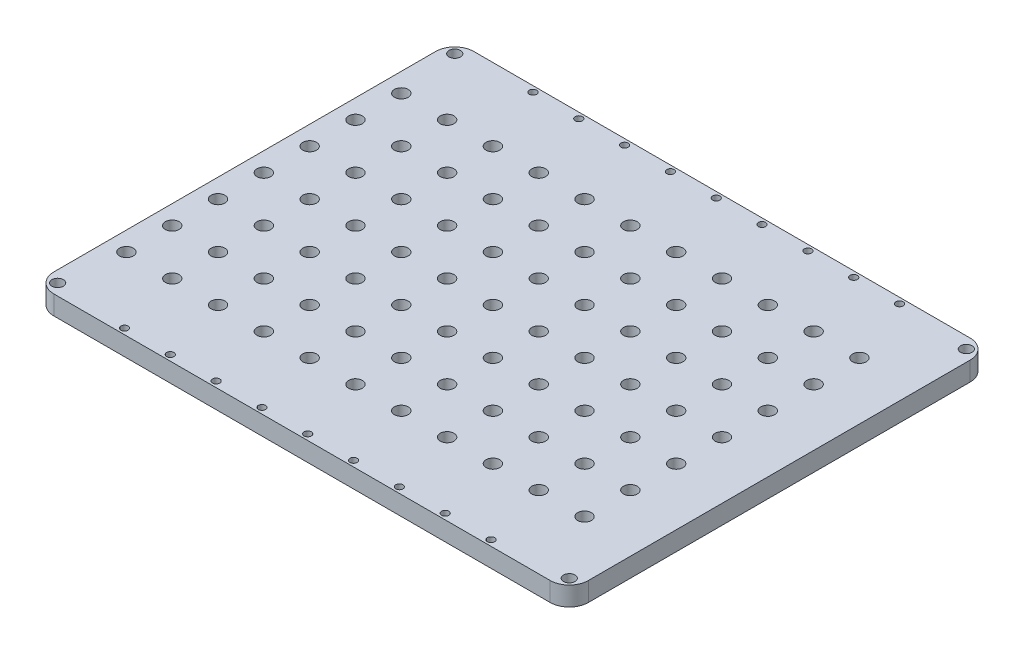
SolidWorks part; units mm, degrees
ref_plane "Front Plane" through (0, 0, 0) normal (0, 0, 1) x (1, 0, 0)
ref_plane "Top Plane" through (0, 0, 0) normal (0, 1, 0) x (1, 0, 0)
ref_plane "Right Plane" through (0, 0, 0) normal (1, 0, 0) x (0, 0, -1)
sketch "Sketch1" plane through (0, 0, 0) normal (0, 1, 0) x (1, 0, 0)
  line L1 (-70, 55) -> (70, 55)
  line L2 (-70, 55) -> (-70, -55)
  line L3 (-70, -55) -> (70, -55)
  line L4 (70, 55) -> (70, -55)
  line L5 (-70, 55) -> (70, -55) construction
  line L6 (-70, -55) -> (70, 55) construction
  point P0 (0, 0)
  dimension "D1" = 110
  dimension "D2" = 140
extrude "Boss-Extrude1" add sketch "Sketch1" along normal blind 5
fillet "Fillet1" radius 5 4 edges at (70, 2.5, -55) (70, 2.5, 55) (-70, 2.5, 55) (-70, 2.5, -55)
sketch "Sketch2" plane through (0, 5, 0) normal (0, 1, 0) x (1, 0, 0)
  line L4 (-68.5355, 53.5355) -> (-67.0011, 52.0011)
  line L8 (67, -50) -> (67, 50)
  line L9 (65, 52) -> (-65, 52)
  line L10 (-67, 50) -> (-67, -50)
  line L11 (-65, -52) -> (65, -52)
  line L12 (67, -50) -> (67, 50)
  line L13 (65, 52) -> (-65, 52)
  line L14 (-67, 50) -> (-67, -50)
  line L15 (-65, -52) -> (65, -52)
  arc A6 (-65, 55) -> (-70, 50) centre (-65, 50) ccw construction
  circle A7 centre (-67.0011, 52.0011) radius 1.5
  arc A8 (67, 50) -> (65, 52) centre (65, 50) ccw
  arc A9 (-65, 52) -> (-67, 50) centre (-65, 50) ccw
  arc A10 (-67, -50) -> (-65, -52) centre (-65, -50) ccw
  arc A11 (65, -52) -> (67, -50) centre (65, -50) ccw
  arc A12 (67, 50) -> (65, 52) centre (65, 50) ccw
  arc A13 (-65, 52) -> (-67, 50) centre (-65, 50) ccw
  arc A14 (-67, -50) -> (-65, -52) centre (-65, -50) ccw
  arc A15 (65, -52) -> (67, -50) centre (65, -50) ccw
  circle A16 centre (66.9989, 52.0011) radius 1.5
  circle A17 centre (66.9989, -51.9989) radius 1.5
  circle A18 centre (-67.0011, -51.9989) radius 1.5
  dimension "D2" = 2
  dimension "D1" = 3
  dimension "D3" = 2
extrude "Cut-Extrude1" cut sketch "Sketch2" against normal blind 5 contours A13 A7 | A7 A13 | A15 A17 | A15 A17 | A14 A18 | A14 A18 | A16 region at (67.1229, 5, 52.1229) region at (66.1833, 5, 51.1833) region at (-67.1248, 5, 52.1224) region at (-66.1845, 5, 51.1832) region at (-66.4442, 5, -51.4442) region at (-66.1844, 5, -51.1844)
sketch "Sketch3" plane through (0, 5, 0) normal (0, 1, 0) x (1, 0, 0)
  line L0 (0, -55) -> (0, -52)
  line L1 (-65, -55) -> (65, -55) construction
  circle A0 centre (0, -53.5) radius 0.95
  circle A1 centre (12, -53.5) radius 0.95
  circle A2 centre (24, -53.5) radius 0.95
  circle A3 centre (36, -53.5) radius 0.95
  circle A4 centre (48, -53.5) radius 0.95
  circle A5 centre (0, -53.5) radius 0.95
  circle A6 centre (12, -53.5) radius 0.95
  circle A7 centre (24, -53.5) radius 0.95
  circle A8 centre (36, -53.5) radius 0.95
  circle A9 centre (-12, -53.5) radius 0.95
  circle A10 centre (0, -53.5) radius 0.95
  circle A11 centre (12, -53.5) radius 0.95
  circle A12 centre (24, -53.5) radius 0.95
  circle A13 centre (-24, -53.5) radius 0.95
  circle A14 centre (-12, -53.5) radius 0.95
  circle A15 centre (0, -53.5) radius 0.95
  circle A16 centre (12, -53.5) radius 0.95
  circle A17 centre (-36, -53.5) radius 0.95
  circle A18 centre (-24, -53.5) radius 0.95
  circle A19 centre (-12, -53.5) radius 0.95
  circle A20 centre (0, -53.5) radius 0.95
  circle A21 centre (-12, -53.5) radius 0.95
  circle A22 centre (-24, -53.5) radius 0.95
  circle A23 centre (-36, -53.5) radius 0.95
  circle A24 centre (-48, -53.5) radius 0.95
  dimension "D2" = 5
  dimension "D1" = 3
  dimension "D3" = 5
extrude "Cut-Extrude2" cut sketch "Sketch3" against normal blind 5 contours A24 | A17 | A13 | A9 | A0 | A1 | A2 | A4 | A3 region at (-12, 5, 53.5) region at (-24, 5, 53.5) region at (-36, 5, 53.5) region at (-48, 5, 53.5)
mirror "Mirror1" about plane through (0, 0, 0) normal (0, 0, 1) of "Cut-Extrude2"
sketch "Sketch4" plane through (0, 5, 0) normal (0, 1, 0) x (1, 0, 0)
  line L0 (-70, 0) -> (-65, 0)
  line L2 (-70, 50) -> (-70, -50) construction
  circle A0 centre (-65, 0) radius 1.8
  circle A1 centre (-65, 12) radius 1.8
  circle A2 centre (-65, 24) radius 1.8
  circle A3 centre (-65, 36) radius 1.8
  circle A4 centre (-65, 0) radius 1.8
  circle A5 centre (-65, 12) radius 1.8
  circle A6 centre (-65, 24) radius 1.8
  circle A7 centre (-65, -12) radius 1.8
  circle A8 centre (-65, 0) radius 1.8
  circle A9 centre (-65, 12) radius 1.8
  circle A10 centre (-65, -24) radius 1.8
  circle A11 centre (-65, -12) radius 1.8
  circle A12 centre (-65, 0) radius 1.8
  circle A13 centre (-65, -12) radius 1.8
  circle A14 centre (-65, -24) radius 1.8
  circle A15 centre (-65, -36) radius 1.8
  dimension "D2" = 4
  dimension "D1" = 5
  dimension "D3" = 4
extrude "Cut-Extrude5" cut sketch "Sketch4" against normal blind 5 contours A3 | A2 | A1 | A0 | A7 | A10 | A15 region at (-65, 5, 1.7491) region at (-65, 5, -12) region at (-65, 5, -24) region at (-65, 5, -36) region at (-65, 5, 12) region at (-65, 5, 24) region at (-65, 5, 36)
pattern_linear "LPattern2" count 11 spacing 12 along (1, 0, 0) of "Cut-Extrude5"
